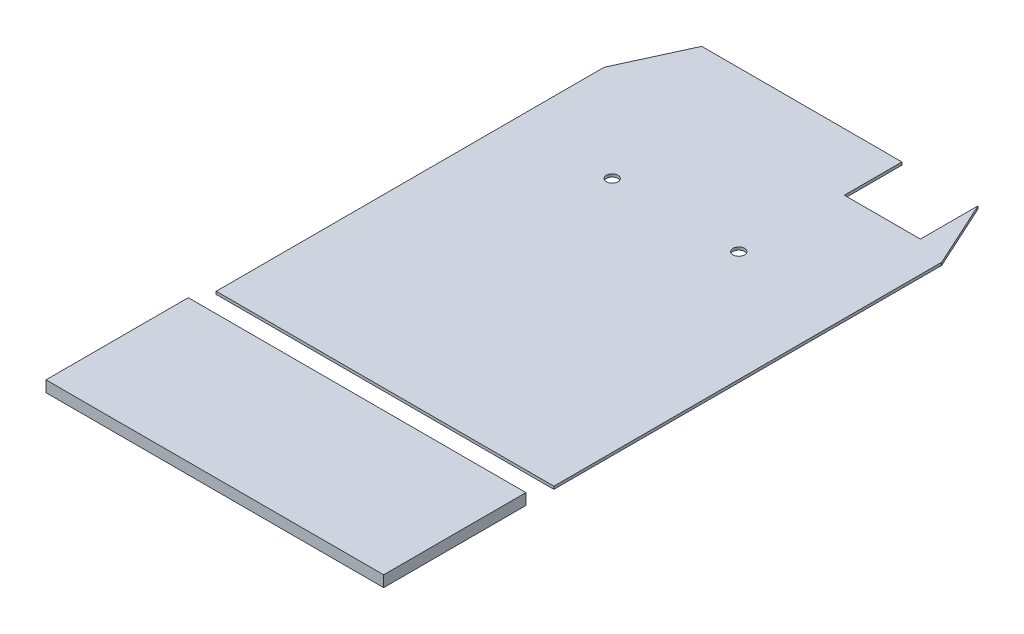
SolidWorks part; units mm, degrees
ref_plane "Front Plane" through (0, 0, 0) normal (0, 0, 1) x (1, 0, 0)
ref_plane "Top Plane" through (0, 0, 0) normal (0, 1, 0) x (1, 0, 0)
ref_plane "Right Plane" through (0, 0, 0) normal (1, 0, 0) x (0, 0, -1)
sketch "Sketch1" plane through (0, 0, 0) normal (0, 1, 0) x (1, 0, 0)
  line L0 (-96.0438, 177.8) -> (35.3219, 177.8)
  line L1 (96.0438, -177.8) -> (-96.0438, -177.8)
  line L2 (96.0438, -177.8) -> (96.0437, 177.8)
  line L4 (-96.0438, -177.8) -> (-96.0438, 177.8)
  line L5 (96.0438, -177.8) -> (-96.0438, 177.8) construction
  line L6 (96.0437, 177.8) -> (-96.0438, -177.8) construction
  line L7 (35.3219, 177.8) -> (35.3219, 145.0362)
  line L8 (35.3219, 145.0362) -> (78.5812, 145.0362)
  line L9 (78.5812, 145.0362) -> (78.5812, 177.8)
  line L10 (78.5812, 177.8) -> (96.0437, 177.8)
  point P0 (0, 0)
  dimension "D1" = 355.6
  dimension "D2" = 192.0875
  dimension "D3" = 43.2594
  dimension "D4" = 17.4625
extrude "Boss-Extrude1" add sketch "Sketch1" along normal blind 1.5875 contours L4 L0 L7 L8 L9 L10 L2 L1
sketch "Sketch2" plane through (0, 1.5875, 0) normal (0, 1, 0) x (1, 0, 0)
  line L0 (96.0438, -177.8) -> (96.0437, 177.8) construction
  line L1 (96.0438, -80.9625) -> (-96.0437, -80.9625)
  line L2 (96.0438, -80.9625) -> (96.0438, -96.8375)
  line L3 (96.0438, -96.8375) -> (-96.0438, -96.8375)
  line L4 (-96.0437, -80.9625) -> (-96.0438, -96.8375)
  line L5 (-96.0438, -177.8) -> (-96.0438, 177.8) construction
  line L6 (-78.5813, 177.8) -> (-96.0438, 139.7)
  line L7 (-96.0438, 177.8) -> (35.3219, 177.8) construction
  line L8 (-96.0438, 139.7) -> (-96.0438, 177.8)
  line L9 (-96.0438, 177.8) -> (-78.5813, 177.8)
  line L13 (96.0438, -177.8) -> (-96.0438, -177.8) construction
  line L14 (96.0437, 139.7) -> (78.5812, 177.8)
  line L15 (78.5812, 177.8) -> (96.0437, 177.8) construction
  line L16 (78.5812, 177.8) -> (96.0437, 177.8)
  line L17 (96.0437, 177.8) -> (96.0437, 139.7)
  dimension "D1" = 15.875
  dimension "D2" = 80.9625
  dimension "D3" = 38.1
extrude "Cut-Extrude1" cut sketch "Sketch2" against normal up to surface (1.5875 mm away) up to face at (28.4758, 0, -80.709)
sketch "Sketch3" plane through (0, 1.5875, 0) normal (0, 1, 0) x (1, 0, 0)
  line L1 (-96.0438, -96.8375) -> (96.0438, -96.8375)
  line L2 (-96.0438, -96.8375) -> (-96.0438, -177.8)
  line L3 (-96.0438, -177.8) -> (96.0438, -177.8)
  line L4 (96.0438, -96.8375) -> (96.0438, -177.8)
extrude "Boss-Extrude2" add sketch "Sketch3" along normal blind 4.7625
sketch "Sketch4" plane through (0, 1.5875, 0) normal (0, 1, 0) x (1, 0, 0)
  circle A0 centre (33.0771, 87.2046) radius 3.2639
  circle A1 centre (-38.9318, 87.2046) radius 3.2639
extrude "Cut-Extrude2" cut sketch "Sketch4" against normal blind 9.906
